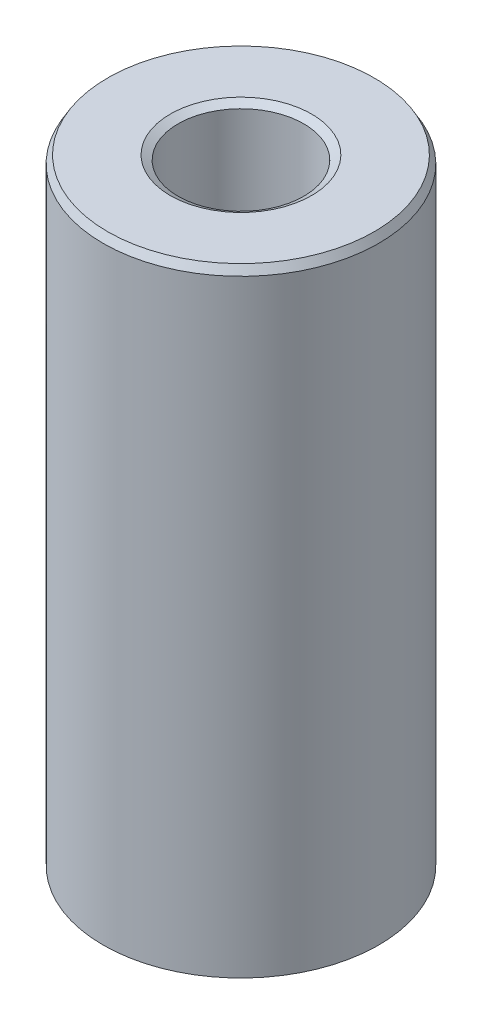
SolidWorks part; units mm, degrees
ref_plane "Front Plane" through (0, 0, 0) normal (0, 0, 1) x (1, 0, 0)
ref_plane "Top Plane" through (0, 0, 0) normal (0, 1, 0) x (1, 0, 0)
ref_plane "Right Plane" through (0, 0, 0) normal (1, 0, 0) x (0, 0, -1)
sketch "Sketch1" plane through (0, 0, 0) normal (0, 1, 0) x (1, 0, 0)
  circle A0 centre (0, 0) radius 60
  dimension "SLEEVE_OD" = 120
extrude "Boss-Extrude1" add sketch "Sketch1" along normal blind 270.0088
sketch "Sketch2" plane through (0, 0, 0) normal (0, 1, 0) x (1, 0, 0)
  circle A0 centre (0, 0) radius 27.3633
  dimension "BORE_D" = 54.7266
extrude "Cut-Extrude1" cut sketch "Sketch2" along normal through all
chamfer "Chamfer1" distance 3.4112 angle 30 4 edges at (0, 270.0088, 27.3633) (0, 0, 27.3633) (0, 0, 60) (0, 270.0088, 60) first distance on face at (0, 270.0088, 27.3633) first distance on face at (0, 0, 27.3633) first distance on face at (0, 270.0088, 60)
